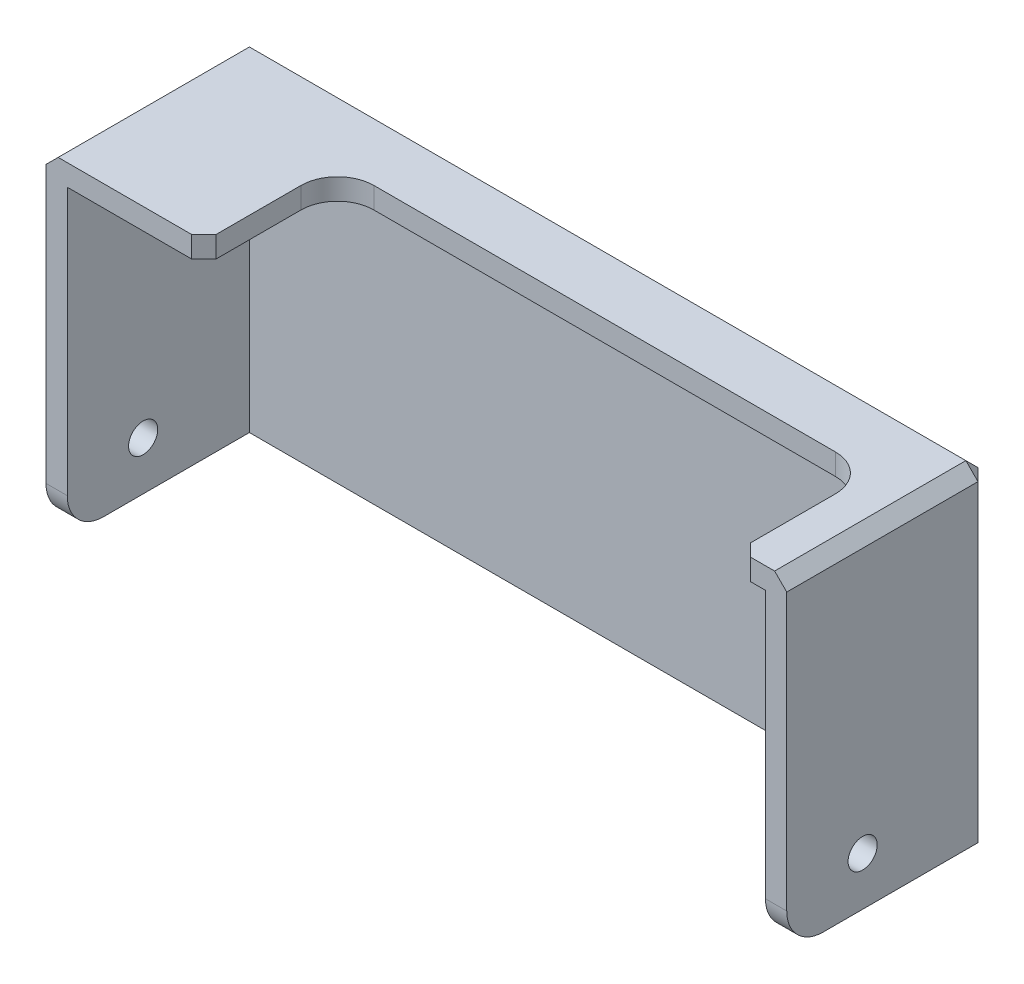
SolidWorks part; units mm, degrees
ref_plane "Front Plane" through (0, 0, 0) normal (0, 0, 1) x (1, 0, 0)
ref_plane "Top Plane" through (0, 0, 0) normal (0, 1, 0) x (1, 0, 0)
ref_plane "Right Plane" through (0, 0, 0) normal (1, 0, 0) x (0, 0, -1)
sketch "Sketch1" plane through (0, 0, 0) normal (0, 0, 1) x (1, 0, 0)
  line L1 (-57.5, -25) -> (57.5, -25)
  line L2 (-57.5, -25) -> (-57.5, 25)
  line L3 (-57.5, 25) -> (57.5, 25)
  line L4 (57.5, -25) -> (57.5, 25)
  line L5 (-57.5, -25) -> (57.5, 25) construction
  line L6 (-57.5, 25) -> (57.5, -25) construction
  point P0 (0, 0)
  dimension "D1" = 50
  dimension "D2" = 115
extrude "Boss-Extrude1" add sketch "Sketch1" along normal blind 30
sketch "Sketch2" plane through (0, 25, 0) normal (0, 1, 0) x (1, 0, 0)
  line L0 (57.5, -30) -> (-57.5, -30) construction
  line L1 (-35, -30) -> (53, -30)
  line L2 (-35, -30) -> (-35, -8)
  line L3 (-35, -8) -> (53, -8)
  line L4 (53, -30) -> (53, -8)
  line L6 (57.5, -30) -> (57.5, 0) construction
  line L7 (-57.5, -30) -> (-57.5, 0) construction
  dimension "D1" = 22.5
  dimension "D2" = 4.5
  dimension "D3" = 22
extrude "Cut-Extrude1" cut sketch "Sketch2" against normal through all
sketch "Sketch3" plane through (0, 0, 30) normal (0, 0, 1) x (1, 0, 0)
  line L0 (53, -25) -> (57.5, -25) construction
  line L1 (57.25, -25) -> (-57.25, -25)
  line L2 (57.25, -25) -> (57.25, 15)
  line L3 (57.25, 15) -> (-57.25, 15)
  line L4 (-57.25, -25) -> (-57.25, 15)
  line L5 (0, 15) -> (0, -25) construction
  line L7 (57.5, 25) -> (53, 25) construction
  dimension "D1" = 114.5
  dimension "D2" = 10
extrude "Cut-Extrude2" [suppressed] cut sketch "Sketch3" against normal blind 30
shell "Shell1" thickness 3.5 removed face at (-35, 0, 19) removed face at (9, 0, 8) removed face at (53, 0, 19) removed face at (55.25, 0, 30) removed face at (4.5, -25, 17) removed face at (-46.25, 0, 30) outward yes
sketch "Sketch6" plane through (-61, 0, 0) normal (-1, 0, 0) x (0, 0, 1)
  line L0 (0, 25) -> (0, -25) construction
  line L1 (30, 25) -> (0, 25) construction
  point P0 (17.5, -17)
  dimension "D1" = 17.5
  dimension "D2" = 42
hole_wizard "M4 Clearance Hole1" positions "Sketch6" profile "Sketch5" hole size "M4" standard "ISO" end condition through all
sketch "Sketch5" plane through (-61, -17, 17.5) normal (0, 1, 0) x (0, 0, 1)
  line L0 (0, 0) -> (0, 122)
  line L1 (0, 122) -> (2.4, 122)
  line L2 (2.4, 122) -> (2.4, 0)
  line L5 (2.4, 0) -> (0, 0)
  line L11 (0, -6.35) -> (0, 107.95) construction
  dimension "Thru Hole Dia." = 4.8
  dimension "Thru Hole Depth" = 122
chamfer "Chamfer1" distance 2 angle 45 8 edges at (0, 28.5, -3.5) (61, 28.5, 13.25) (61, 1.75, -3.5) (0, -25, -3.5) (-61, 1.75, -3.5) (-61, 28.5, 13.25) (53, 26.75, 30) (-35, 26.75, 30)
fillet "Fillet1" radius 6 2 edges at (-35, 26.75, 8) (53, 26.75, 8)
fillet "Fillet2" radius 6 2 edges at (59.25, -25, 30) (-59.25, -25, 30)
